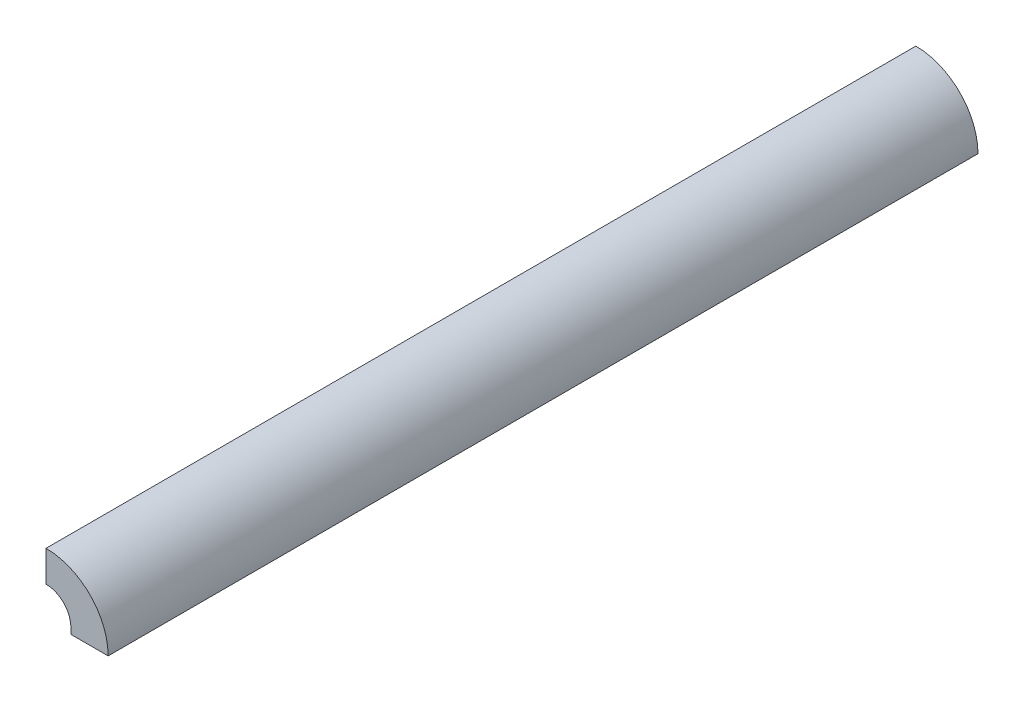
SolidWorks part; units mm, degrees
ref_plane "Front Plane" through (0, 0, 0) normal (0, 0, 1) x (1, 0, 0)
ref_plane "Top Plane" through (0, 0, 0) normal (0, 1, 0) x (1, 0, 0)
ref_plane "Right Plane" through (0, 0, 0) normal (1, 0, 0) x (0, 0, -1)
sketch "Sketch1" plane through (0, 0, 0) normal (0, 0, 1) x (1, 0, 0)
  line L0 (0, 0) -> (0, 25)
  line L1 (0, 0) -> (25, 0)
  arc A0 (25, 0) -> (0, 25) centre (0, 0) ccw
  dimension "D1" = 50
extrude "Boss-Extrude1" add sketch "Sketch1" along normal blind 350 contours A0 L0 L1
sketch "Sketch2" plane through (0, 0, 0) normal (-1, 0, 0) x (0, 0, 1)
  line L1 (350, 0) -> (350, 12.5)
  line L2 (350, 0) -> (350, 25) construction
  line L3 (350, 12.5) -> (208.0719, 12.5)
  line L5 (350, 0) -> (0, 0) construction
  line L6 (175, 0) -> (350, 0)
  arc A0 (208.0719, 12.5) -> (175, 0) centre (208.0719, -37.5) ccw
  point P12 (175.4777, 0)
  dimension "D1" = 50
extrude "Cut-Extrude1" cut sketch "Sketch2" against normal blind 10 contours L3 A0 L6 L1
fillet "Fillet1" radius 10 2 edges at (10, 12.5, 279.0359) (10, 9.2707, 190.3942)
